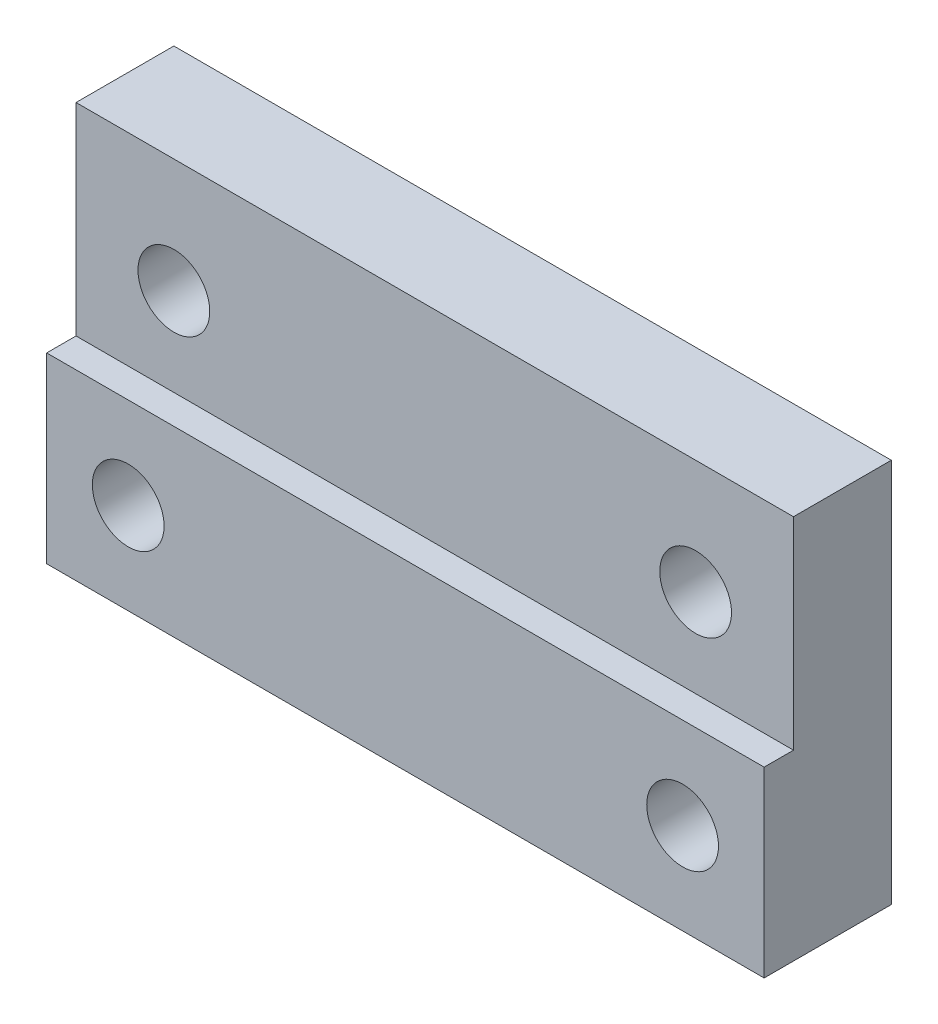
SolidWorks part; units mm, degrees
ref_plane "Front Plane" through (0, 0, 0) normal (0, 0, 1) x (1, 0, 0)
ref_plane "Top Plane" through (0, 0, 0) normal (0, 1, 0) x (1, 0, 0)
ref_plane "Right Plane" through (0, 0, 0) normal (1, 0, 0) x (0, 0, -1)
sketch "Sketch1" plane through (0, 0, 0) normal (0, 1, 0) x (1, 0, 0)
  line L0 (-11, -1.05) -> (11, -1.05)
  line L1 (11, 1.95) -> (-11, 1.95)
  line L2 (11, 1.95) -> (11, -1.95)
  line L3 (11, -1.95) -> (-11, -1.95)
  line L4 (-11, 1.95) -> (-11, -1.95)
  line L5 (11, 1.95) -> (-11, -1.95) construction
  line L6 (11, -1.95) -> (-11, 1.95) construction
  point P0 (0, 0)
  dimension "D1" = 3
  dimension "D2" = 0.9
  dimension "D3" = 22
extrude "Boss-Extrude1" add sketch "Sketch1" along normal blind 11.8 contours L1 L4 L0 L2 region at (0, 0, -0.45)
extrude "Boss-Extrude2" add sketch "Sketch1<3>" along normal blind 5.6 contours L0 L4 L3 L2 region at (0, 0, 1.5)
sketch "Sketch1<3>" plane through (0, 0, 0) normal (0, 1, 0) x (1, 0, 0) same geometry as "Sketch1"
sketch "Sketch2" plane through (0, 0, -1.95) normal (0, 0, -1) x (-1, 0, 0)
  line L0 (2.2, 0) -> (-2.2, 0) construction
  line L1 (-11, 11.8) -> (11, 11.8) construction
  circle A0 centre (-8.5, 2.8) radius 1.1
  circle A1 centre (-8, 8.3) radius 1.1
  dimension "D1" = 2.2
  dimension "D2" = 2.2
  dimension "D3" = 8.5
  dimension "D4" = 8
  dimension "D5" = 2.8
  dimension "D6" = 3.5
extrude "Cut-Extrude1" cut sketch "Sketch2" against normal up to surface (3.9 mm away) contours A0 | A1 region at (8.5, 2.8, -1.95) region at (8, 8.3, -1.95) up to face at (0, 2.8, 1.95)
mirror "Mirror1" about plane through (0, 0, 0) normal (1, 0, 0) of "Cut-Extrude1"
move or copy body "Body-Move/Copy1" [suppressed] bodies to move or copy 109
